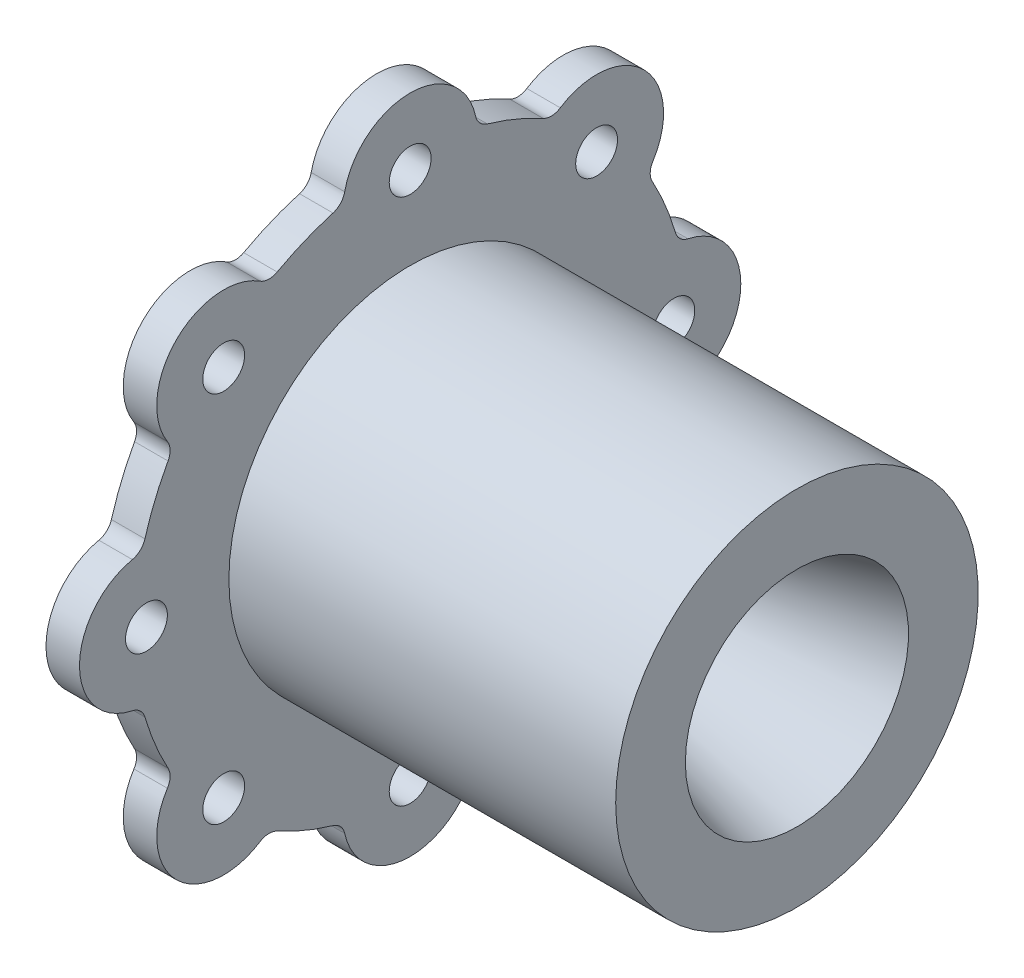
SolidWorks part; units mm, degrees
ref_plane "Front Plane" through (0, 0, 0) normal (0, 0, 1) x (1, 0, 0)
ref_plane "Top Plane" through (0, 0, 0) normal (0, 1, 0) x (1, 0, 0)
ref_plane "Right Plane" through (0, 0, 0) normal (1, 0, 0) x (0, 0, -1)
sketch "Sketch1" plane through (0, 0, 0) normal (0, 0, 1) x (1, 0, 0)
  line L20 (0, 0) -> (32.997, 0) construction
  line L33 (20, 6.946) -> (26.5, 6.946)
  line L34 (20, 6.946) -> (0, 25.4)
  line L37 (0, 25.4) -> (0, 51)
  line L38 (0, 51) -> (5.08, 51)
  line L39 (5.08, 51) -> (5.08, 27.5)
  line L43 (63.7608, 27.5) -> (63.7608, 16.93)
  line L52 (63.7608, 16.93) -> (26.5, 6.946)
  line L53 (63.7608, 27.5) -> (5.08, 27.5)
  point P0 (0, 0)
  point P1 (2.54, 51)
  point P12 (20, 6.946)
  point P24 (26.5, 6.946)
  dimension "D1" = 6.946
  dimension "D2" = 25.4
  dimension "D5" = 5.08
  dimension "D7" = 20
  dimension "D10" = 15
  dimension "D8" = 16.93
  dimension "D3" = 27.5
  dimension "D4" = 51
  dimension "D6" = 6.5
revolve "Nozzle" add sketch "Sketch1" angle 360 about L20
fillet "Rao inlet radius" radius 20.8 1 edges at (26.5, 0, 6.946)
fillet "Rao outlet radius" radius 5.3067 1 edges at (20, 0, 6.946)
sketch "Sketch2" plane through (0, 0, 0) normal (-1, 0, 0) x (0, 0, 1)
  point P0 (40.005, 0)
  point P1 (28.2878, -28.2878)
  point P5 (0, -40.005)
  point P6 (-28.2878, -28.2878)
  point P7 (-40.005, 0)
  point P8 (-28.2878, 28.2878)
  point P9 (0, 40.005)
  point P10 (28.2878, 28.2878)
  point P11 (0, 0)
  dimension "D1" = 40.005
  dimension "D2" = 8
hole_wizard "1/4 (0.25) Diameter Hole1" positions "Sketch2" profile "Sketch3" hole size "1/4" standard "ANSI Inch" end condition through all
sketch "Sketch3" plane through (0, 0, 40.005) normal (0, 1, 0) x (0, 0, 1)
  line L0 (0, 0) -> (0, 63.7608)
  line L1 (0, 63.7608) -> (3.175, 63.7608)
  line L2 (3.175, 63.7608) -> (3.175, 0)
  line L5 (3.175, 0) -> (0, 0)
  line L11 (0, -6.35) -> (0, 107.95) construction
  dimension "Thru Hole Dia." = 6.35
  dimension "Thru Hole Depth" = 63.7608
sketch "Sketch5" plane through (0, 0, 0) normal (1, 0, 0) x (0, 0, -1)
  arc A32 (9.9319, 42.1459) -> (-9.9319, 42.1459) centre (0, 40.005) ccw
  arc A33 (17.8566, 37.9156) -> (11.7054, 40.2422) centre (0, 0) ccw
  arc A51 (-11.7054, 40.2422) -> (-14.1838, 39.4369) centre (0, 0) ccw
  arc A69 (9.9319, 42.1459) -> (11.7054, 40.2422) centre (12.4149, 42.6811) ccw
  arc A70 (-9.9319, 42.1459) -> (-11.7054, 40.2422) centre (-12.4149, 42.6811) cw
  arc A72 (36.8245, 22.7787) -> (22.7787, 36.8245) centre (28.2878, 28.2878) ccw
  arc A73 (39.4369, 14.1838) -> (36.7325, 20.1785) centre (0, 0) ccw
  arc A74 (20.1785, 36.7325) -> (17.8566, 37.9156) centre (0, 0) ccw
  arc A75 (36.8245, 22.7787) -> (36.7325, 20.1785) centre (38.9587, 21.4014) ccw
  arc A76 (22.7787, 36.8245) -> (20.1785, 36.7325) centre (21.4014, 38.9587) cw
  arc A77 (42.1459, -9.9319) -> (42.1459, 9.9319) centre (40.005, 0) ccw
  arc A78 (37.9156, -17.8566) -> (40.2422, -11.7054) centre (0, 0) ccw
  arc A79 (40.2422, 11.7054) -> (39.4369, 14.1838) centre (0, 0) ccw
  arc A80 (42.1459, -9.9319) -> (40.2422, -11.7054) centre (42.6811, -12.4149) ccw
  arc A81 (42.1459, 9.9319) -> (40.2422, 11.7054) centre (42.6811, 12.4149) cw
  arc A82 (22.7787, -36.8245) -> (36.8245, -22.7787) centre (28.2878, -28.2878) ccw
  arc A83 (14.1838, -39.4369) -> (20.1785, -36.7325) centre (0, 0) ccw
  arc A84 (36.7325, -20.1785) -> (37.9156, -17.8566) centre (0, 0) ccw
  arc A85 (22.7787, -36.8245) -> (20.1785, -36.7325) centre (21.4014, -38.9587) ccw
  arc A86 (36.8245, -22.7787) -> (36.7325, -20.1785) centre (38.9587, -21.4014) cw
  arc A87 (-9.9319, -42.1459) -> (9.9319, -42.1459) centre (0, -40.005) ccw
  arc A88 (-14.1838, -39.4369) -> (-11.7054, -40.2422) centre (0, 0) ccw
  arc A89 (11.7054, -40.2422) -> (14.1838, -39.4369) centre (0, 0) ccw
  arc A90 (-9.9319, -42.1459) -> (-11.7054, -40.2422) centre (-12.4149, -42.6811) ccw
  arc A91 (9.9319, -42.1459) -> (11.7054, -40.2422) centre (12.4149, -42.6811) cw
  arc A92 (-36.8245, -22.7787) -> (-22.7787, -36.8245) centre (-28.2878, -28.2878) ccw
  arc A93 (-37.9156, -17.8566) -> (-36.7325, -20.1785) centre (0, 0) ccw
  arc A94 (-20.1785, -36.7325) -> (-14.1838, -39.4369) centre (0, 0) ccw
  arc A95 (-36.8245, -22.7787) -> (-36.7325, -20.1785) centre (-38.9587, -21.4014) ccw
  arc A96 (-22.7787, -36.8245) -> (-20.1785, -36.7325) centre (-21.4014, -38.9587) cw
  arc A97 (-42.1459, 9.9319) -> (-42.1459, -9.9319) centre (-40.005, 0) ccw
  arc A98 (-39.4369, 14.1838) -> (-40.2422, 11.7054) centre (0, 0) ccw
  arc A99 (-40.2422, -11.7054) -> (-37.9156, -17.8566) centre (0, 0) ccw
  arc A100 (-42.1459, 9.9319) -> (-40.2422, 11.7054) centre (-42.6811, 12.4149) ccw
  arc A101 (-42.1459, -9.9319) -> (-40.2422, -11.7054) centre (-42.6811, -12.4149) cw
  arc A102 (-22.7787, 36.8245) -> (-36.8245, 22.7787) centre (-28.2878, 28.2878) ccw
  arc A103 (-14.1838, 39.4369) -> (-20.1785, 36.7325) centre (0, 0) ccw
  arc A104 (-36.7325, 20.1785) -> (-39.4369, 14.1838) centre (0, 0) ccw
  arc A105 (-22.7787, 36.8245) -> (-20.1785, 36.7325) centre (-21.4014, 38.9587) ccw
  arc A106 (-36.8245, 22.7787) -> (-36.7325, 20.1785) centre (-38.9587, 21.4014) cw
  point P69 (0, 0)
  point P78 (-10.1385, 40.6652)
  dimension "D1" = 8
  dimension "D3" = 41.91
  dimension "D4" = 2.54
  dimension "D2" = 10.16
  dimension "D5" = 40.005
extrude "Cut-Extrude1" cut sketch "Sketch5" along normal up to surface (5.08 mm away) flip side to cut up to face at (5.08, 0, 43.18)
equation "\"radius\"= 1in"
equation "\"Flange\"= 2.35cm"
equation "\"Length\"= 2cm"
equation "\"Flange_Thickness\"= 0.2in"
equation "\"offset\"= 0.625cm"
equation "\"D2@Sketch1\"=\"radius\""
equation "\"throat\"= 0.6946cm"
equation "\"hole_dia\"= 0.66cm"
equation "\"D1@Sketch1\"=\"throat\""
equation "\"D5@Sketch1\"=\"Flange_Thickness\""
equation "\"D7@Sketch1\"=\"Length\""
equation "\"Seal_dia\"= 2.5cm"
equation "\"Seal_depth\"= 0.1cm"
equation "\"Seal_width\"= 0.15cm"
equation "\"Nozzle_angle\"= 15"
equation "\"D10@Sketch1\"=\"Nozzle_angle\""
equation "\"nozzle_length\"= 6.34"
equation "\"bolt_head_dia\"=2.3795"
equation "\"bolt_rad\"= \"radius\" + 0.5 * \"Flange\" + ( ( \"offset\" ^ 2 ) - ( \"Flange_Thickness\" ^ 2 ) ) ^ 0.5cm"
equation "\"scallop_inner_dia\"= 3.3in"
equation "\"exit_rad\"= 1.693cm"
equation "\"D8@Sketch1\"=\"exit_rad\""
equation "\"outside_dia\"= 2.75cm"
equation "\"D3@Sketch1\"=\"outside_dia\""
equation "\"D4@Sketch1\"=\"outside_dia\"+\"Flange\""
equation "\"Scallop_OD\"= 0.8in"
equation "\"D1@Rao outlet radius\" = 2 * 0.382 * \"throat\""
equation "\"D3\" = \"Scallop_OD\" / 2"
equation "\"D4\" = \"scallop_inner_dia\" / 2"
